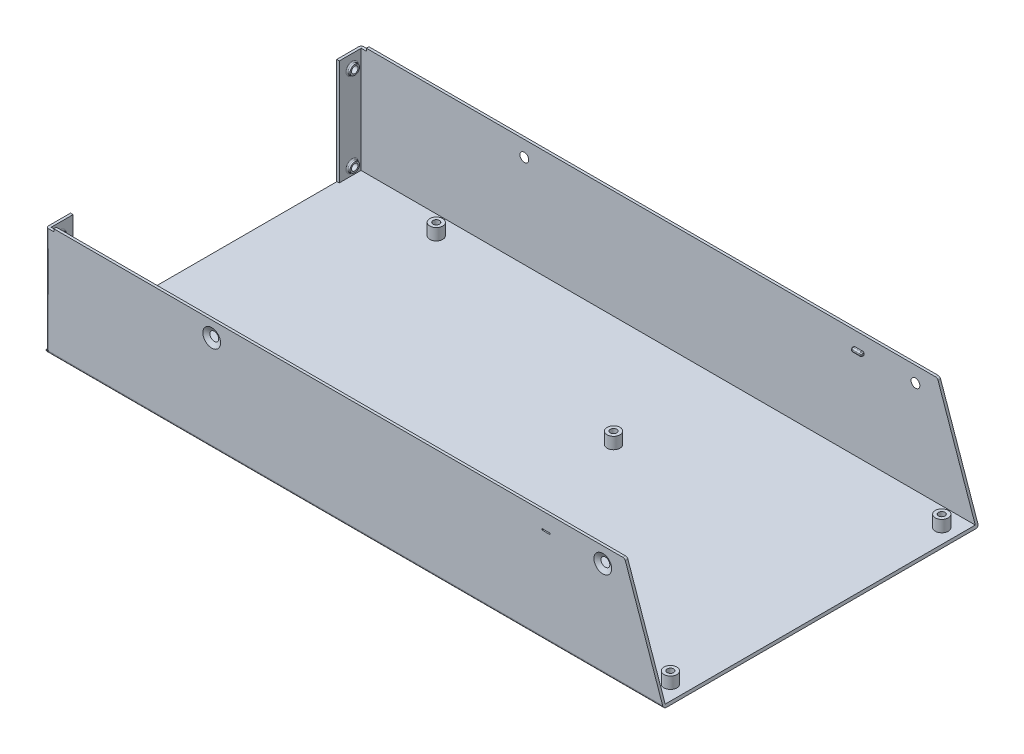
SolidWorks part; units mm, degrees
ref_plane "Front Plane" through (0, 0, 0) normal (0, 0, 1) x (1, 0, 0)
ref_plane "Top Plane" through (0, 0, 0) normal (0, 1, 0) x (1, 0, 0)
ref_plane "Right Plane" through (0, 0, 0) normal (1, 0, 0) x (0, 0, -1)
sketch "Sketch1" plane through (0, 0, 0) normal (1, 0, 0) x (0, 0, -1)
  line L0 (-60, -20.5) -> (-60, 21.5)
  line L1 (-61, -21.5) -> (61, -21.5)
  line L2 (-61, -21.5) -> (-61, 21.5)
  line L3 (-61, 21.5) -> (-60, 21.5)
  line L4 (61, -21.5) -> (61, 21.5)
  line L5 (-61, -21.5) -> (61, 21.5) construction
  line L6 (-61, 21.5) -> (61, -21.5) construction
  line L7 (60, 21.5) -> (61, 21.5)
  line L8 (60, -20.5) -> (60, 21.5)
  line L9 (-60, -20.5) -> (60, -20.5)
  line L10 (-60, -20.5) -> (-60, 20.5) construction
  line L11 (60, -20.5) -> (60, 20.5) construction
  line L12 (-60, 20.5) -> (60, 20.5) construction
  line L14 (-61, 21.5) -> (61, 21.5) construction
  point P0 (0, 0)
  dimension "D1" = 43
  dimension "D2" = 122
  dimension "D3" = 1
extrude "Boss-Extrude1" add sketch "Sketch1" along normal blind 239
sketch "Sketch2" plane through (0, 0, 61) normal (0, 0, 1) x (1, 0, 0)
  line L2 (239, -21.5) -> (223.99, 21.5)
  line L3 (239, 21.5) -> (0, 21.5) construction
  line L4 (223.99, 21.5) -> (239, 21.5)
  line L5 (239, 21.5) -> (239, -21.5)
extrude "Cut-Extrude1" cut sketch "Sketch2" against normal up to surface (122 mm away) up to face at (119.5, 0, -61)
sketch "Sketch3" plane through (0, 0, 61) normal (0, 0, 1) x (1, 0, 0)
  line L1 (0, 21.5) -> (3, 21.5)
  line L2 (0, 21.5) -> (0, 20.5)
  line L3 (0, 20.5) -> (3, 20.5)
  line L4 (3, 21.5) -> (3, 20.5)
  dimension "D1" = 1
  dimension "D2" = 3
extrude "Cut-Extrude2" cut sketch "Sketch3" against normal up to surface (122 mm away) up to face at (115.7475, 0, -61)
hole_wizard "Ø3.4 (3.4) Diameter Hole1" positions "Sketch5" profile "Sketch4" hole size "Ø3.4" standard "ANSI Metric"
sketch "Sketch5" plane through (0, 0, 61) normal (0, 0, 1) x (1, 0, 0)
  line L0 (0, 20.5) -> (0, -21.5) construction
  line L1 (223.99, 21.5) -> (3, 21.5) construction
  point P0 (64.13, 15.5)
  point P2 (215.5, 15.5)
  dimension "D1" = 64.13
  dimension "D2" = 151.37
  dimension "D3" = 6
  dimension "D4" = 6
sketch "Sketch4" plane through (64.13, 15.5, 61) normal (1, 0, 0) x (0, -1, 0)
  line L0 (0, 0) -> (0, 2.8215)
  line L1 (0, 2.8215) -> (1.7, 1.8)
  line L2 (1.7, 1.8) -> (1.7, 0)
  line L5 (1.7, 0) -> (0, 0)
  line L10 (0, 2.8215) -> (-1.7, 1.8) construction
  line L11 (0, -6.35) -> (0, 107.95) construction
  dimension "Hole Dia." = 3.4
  dimension "Hole Depth" = 1.8
  dimension "Drill Angle" = 118
draft "Draft5" type of draft neutral plane draft angle 60 faces to draft 1 face at (65.83, 15.5, 61) neutral plane through (239, -20.5, 60) neutral plane normal (0, 0, -1) reverse direction yes parameters "D1"=60
draft "Draft7" type of draft neutral plane draft angle 60 faces to draft 1 face at (217.2, 15.5, 61) neutral plane through (239, -20.5, 60) neutral plane normal (0, 0, -1) reverse direction yes parameters "D1"=60
sketch "Sketch6" plane through (0, 0, 61) normal (0, 0, 1) x (1, 0, 0)
  line L0 (223.99, 21.5) -> (3, 21.5) construction
  line L1 (191.53, 14.5) -> (195.53, 14.5)
  line L2 (191.53, 14.5) -> (191.53, 16)
  line L3 (191.53, 16) -> (195.53, 16)
  line L4 (195.53, 14.5) -> (195.53, 16)
  line L5 (191.53, 14.5) -> (195.53, 16) construction
  line L6 (191.53, 16) -> (195.53, 14.5) construction
  circle A0 centre (64.13, 15.5) radius 3.4321 construction
  point P0 (193.53, 15.25)
  dimension "D1" = 129.4
  dimension "D2" = 6.25
  dimension "D3" = 1.5
  dimension "D4" = 4
extrude "Boss-Extrude2" add sketch "Sketch6" against normal blind 2
sketch "Sketch7" plane through (0, 0, 61) normal (0, 0, 1) x (1, 0, 0)
  line L14 (192.03, 15.5) -> (192.03, 15)
  line L15 (192.03, 15) -> (195.03, 15)
  line L16 (195.03, 15) -> (195.03, 15.5)
  line L17 (195.03, 15.5) -> (192.03, 15.5)
extrude "Cut-Extrude3" cut sketch "Sketch7" against normal blind 1
fillet "Fillet1" radius 0.5 8 edges at (191.53, 14.5, 59.5) (195.53, 14.5, 59.5) (191.53, 16, 59.5) (195.53, 16, 59.5) (193.53, 14.5, 59) (191.53, 15.25, 59) (193.53, 16, 59) (195.53, 15.25, 59)
mirror "Mirror1" about plane through (0, 0, 0) normal (0, 0, 1) of "Ø3.4 (3.4) Diameter Hole1", "Cut-Extrude3", "Boss-Extrude2"
draft "Draft8" type of draft neutral plane draft angle 60 faces to draft 1 face at (213.8, 15.5, -61) neutral plane through (239, -20.5, -60) neutral plane normal (0, 0, 1) reverse direction yes parameters "D1"=60
draft "Draft9" type of draft neutral plane draft angle 60 faces to draft 1 face at (62.43, 15.5, -61) neutral plane through (239, -20.5, -60) neutral plane normal (0, 0, 1) reverse direction yes parameters "D1"=60
fillet "Fillet3" radius 0.5 8 edges at (191.53, 15.25, -59) (191.53, 16, -59.5) (193.53, 16, -59) (195.53, 15.25, -59) (195.53, 16, -59.5) (191.53, 14.5, -59.5) (193.53, 14.5, -59) (195.53, 14.5, -59.5)
sketch "Sketch8" plane through (0, 0, -60) normal (0, 0, 1) x (1, 0, 0)
  line L0 (238.6509, -20.5) -> (0, -20.5) construction
  line L1 (0, 20.5) -> (1, 20.5)
  line L2 (0, 20.5) -> (0, -20.5)
  line L3 (0, -20.5) -> (1, -20.5)
  line L4 (1, 20.5) -> (1, -20.5)
  dimension "D1" = 1
extrude "Boss-Extrude3" add sketch "Sketch8" along normal blind 8.5
sketch "Sketch9" plane through (0, 0, 0) normal (-1, 0, 0) x (0, 0, 1)
  line L1 (-51.5, -20.5) -> (-61, -20.5)
  line L2 (-51.5, -20.5) -> (-51.5, -20.4)
  line L3 (-51.5, -20.4) -> (-61, -20.4)
  line L4 (-61, -20.5) -> (-61, -20.4)
  dimension "D1" = 9.5
  dimension "D2" = 0.1
extrude "Cut-Extrude4" cut sketch "Sketch9" against normal blind 1
sketch "Sketch10" plane through (1, 0, 0) normal (1, 0, 0) x (0, 0, -1)
  line L0 (51.5, 20.5) -> (60, 20.5) construction
  line L1 (60, -20.4) -> (60, 20.5) construction
  line L2 (51.5, -20.4) -> (60, -20.4) construction
  circle A0 centre (56.5, 15.5) radius 2
  circle A1 centre (56.5, -17.15) radius 2
  dimension "D1" = 4
  dimension "D2" = 5
  dimension "D3" = 3.5
  dimension "D4" = 4
  dimension "D5" = 3.5
  dimension "D6" = 3.25
extrude "Boss-Extrude4" add sketch "Sketch10" along normal blind 1
hole_wizard "M3x0.5 Tapped Hole1" positions "Sketch12" profile "Sketch11" tap size "M3x0.5" standard "ANSI Metric"
sketch "Sketch12" plane through (2, 0, 0) normal (1, 0, 0) x (0, 0, -1)
  circle A0 centre (56.5, 15.5) radius 2 construction
  circle A1 centre (56.5, -17.15) radius 2 construction
  point P0 (56.5, 15.5)
  point P2 (56.5, -17.15)
sketch "Sketch11" plane through (2, 15.5, -56.5) normal (0, 1, 0) x (0, 0, -1)
  line L0 (0, 0) -> (0, 2.7511)
  line L1 (0, 2.7511) -> (1.25, 2)
  line L2 (1.25, 2) -> (1.25, 0)
  line L5 (1.25, 0) -> (0, 0)
  line L10 (0, 2.7511) -> (-1.25, 2) construction
  line L11 (0, -6.35) -> (0, 107.95) construction
  dimension "Tap Drill Dia." = 2.5
  dimension "Tap Drill Depth" = 2
  dimension "Drill Angle" = 118
cosmetic thread "Hole Thread1" parameters "D1"=2, "D2"=3
cosmetic thread "Hole Thread2" parameters "D1"=2, "D2"=3
draft "Draft11" type of draft neutral plane draft angle 10 faces to draft 1 face at (2, 17.5, -56.5) neutral plane through (1, 20.5, -51.5) neutral plane normal (1, 0, 0) parameters "D1"=10
fillet "Fillet5" radius 0.5 1 edges at (1, 13.5, -56.5)
draft "Draft12" type of draft neutral plane draft angle 10 faces to draft 1 face at (2, -15.15, -56.5) neutral plane through (1, 20.5, -51.5) neutral plane normal (1, 0, 0) parameters "D1"=10
fillet "Fillet6" radius 0.5 1 edges at (1, -19.15, -56.5)
mirror "Mirror4" about plane through (0, 0, 0) normal (0, 0, 1) of "Fillet5", "Fillet6", "Boss-Extrude4", "Cut-Extrude4", "M3x0.5 Tapped Hole1", "Boss-Extrude3", "Draft12", "Draft11"
fillet "Fillet7" radius 1 2 edges at (119.5, -21.5, -61) (0, -21, -61)
fillet "Fillet9" radius 1 2 edges at (119.5, -21.5, 61) (0, 0.05, 61)
sketch "Sketch13" plane through (0, -20.5, 0) normal (0, 1, 0) x (1, 0, 0)
  line L0 (0, 61) -> (0, -61) construction
  line L1 (1, -61) -> (238.6509, -61) construction
  circle A0 centre (37.37, 52.68) radius 2.5
  circle A1 centre (233, 52.68) radius 2.5
  circle A2 centre (233, -52.32) radius 2.5
  circle A3 centre (12, -52.32) radius 2.5
  circle A4 centre (141.65, 17.01) radius 2.5
  dimension "D1" = 5
  dimension "D2" = 12
  dimension "D3" = 8.68
  dimension "D4" = 221
  dimension "D5" = 8.68
  dimension "D6" = 129.65
  dimension "D7" = 69.33
  dimension "D8" = 105
  dimension "D9" = 37.37
  dimension "D10" = 195.63
  dimension "D11" = 105
extrude "Boss-Extrude5" add sketch "Sketch13" along normal blind 4.5
hole_wizard "M3x0.5 Tapped Hole2" positions "Sketch15" profile "Sketch14" tap size "M3x0.5" standard "ANSI Metric"
sketch "Sketch15" plane through (0, -16, 0) normal (0, 1, 0) x (1, 0, 0)
  circle A0 centre (233, -52.32) radius 2.5 construction
  circle A1 centre (233, 52.68) radius 2.5 construction
  circle A2 centre (141.65, 17.01) radius 2.5 construction
  circle A3 centre (37.37, 52.68) radius 2.5 construction
  circle A4 centre (12, -52.32) radius 2.5 construction
  point P0 (37.37, 52.68)
  point P2 (233, 52.68)
  point P4 (141.65, 17.01)
  point P6 (12, -52.32)
  point P8 (233, -52.32)
sketch "Sketch14" plane through (37.37, -16, -52.68) normal (1, 0, 0) x (0, 0, 1)
  line L0 (0, 0) -> (0, 5.2511)
  line L1 (0, 5.2511) -> (1.25, 4.5)
  line L2 (1.25, 4.5) -> (1.25, 0)
  line L5 (1.25, 0) -> (0, 0)
  line L10 (0, 5.2511) -> (-1.25, 4.5) construction
  line L11 (0, -6.35) -> (0, 107.95) construction
  dimension "Tap Drill Dia." = 2.5
  dimension "Tap Drill Depth" = 4.5
  dimension "Drill Angle" = 118
cosmetic thread "Hole Thread3" parameters "D1"=4.5, "D2"=3
cosmetic thread "Hole Thread4" parameters "D1"=4.5, "D2"=3
cosmetic thread "Hole Thread5" parameters "D1"=4.5, "D2"=3
cosmetic thread "Hole Thread6" parameters "D1"=4.5, "D2"=3
cosmetic thread "Hole Thread7" parameters "D1"=4.5, "D2"=3
fillet "Fillet10" radius 1 2 edges at (223.99, 21.5, 60.5) (223.99, 21.5, -60.5)
